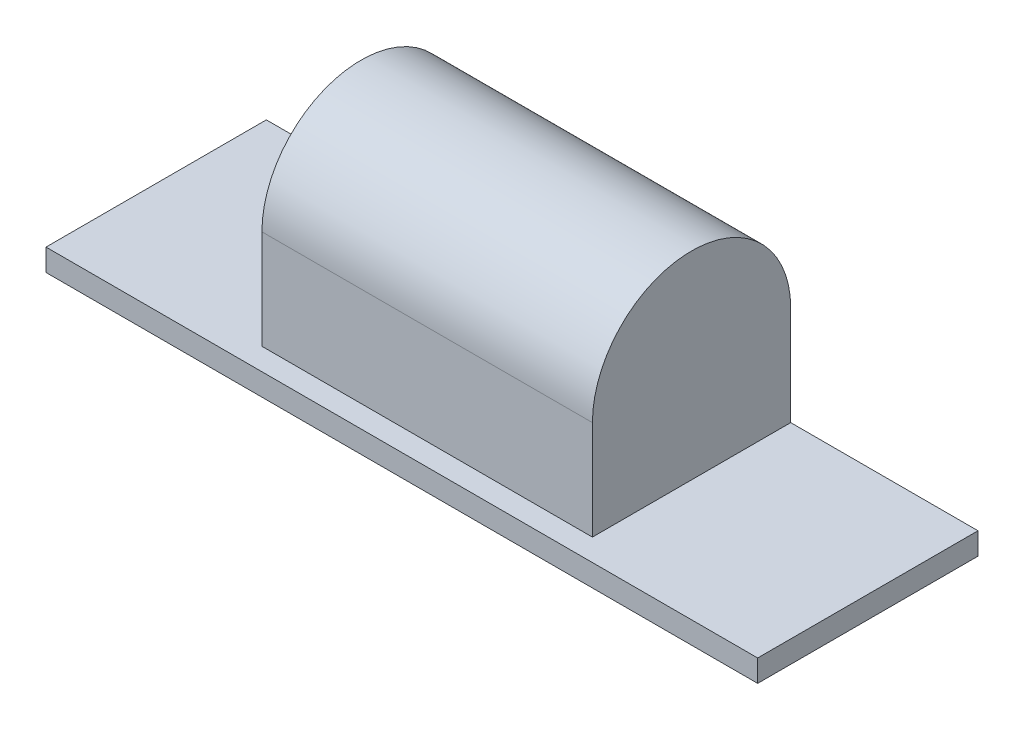
SolidWorks part; units mm, degrees
ref_plane "Front Plane" through (0, 0, 0) normal (0, 0, 1) x (1, 0, 0)
ref_plane "Top Plane" through (0, 0, 0) normal (0, 1, 0) x (1, 0, 0)
ref_plane "Right Plane" through (0, 0, 0) normal (1, 0, 0) x (0, 0, -1)
sketch "Sketch1" plane through (0, 0, 0) normal (0, 1, 0) x (1, 0, 0)
  line L1 (-32.0145, 14.529) -> (32.5855, 14.529)
  line L2 (-32.0145, 14.529) -> (-32.0145, -5.471)
  line L3 (-32.0145, -5.471) -> (32.5855, -5.471)
  line L4 (32.5855, 14.529) -> (32.5855, -5.471)
  line L5 (-14.4145, 14.529) -> (15.5855, 14.529)
  line L6 (-14.4145, 14.529) -> (-14.4145, -3.471)
  line L7 (-14.4145, -3.471) -> (15.5855, -3.471)
  line L8 (15.5855, 14.529) -> (15.5855, -3.471)
  dimension "D1" = 64.6
  dimension "D2" = 20
  dimension "D3" = 18
  dimension "D4" = 30
  dimension "D5" = 17
extrude "Boss-Extrude1" add sketch "Sketch1" along normal blind 2 contours L1 L8 L7 L6 L2 L3 L4 region at (-23.2145, 0, -13.8527)
extrude "Boss-Extrude2" add sketch "Sketch1<3>" along normal blind 20 contours L8 L1 L6 L7 region at (0.5855, 0, -5.529)
sketch "Sketch1<3>" plane through (0, 0, 0) normal (0, 1, 0) x (1, 0, 0) same geometry as "Sketch1"
sketch "Sketch2" plane through (-14.4145, 0, 0) normal (-1, 0, 0) x (0, 0, 1)
  line L0 (-14.529, 11) -> (-14.529, 20)
  line L1 (-14.529, 20) -> (3.471, 20)
  line L2 (3.471, 20) -> (3.471, 11)
  circle A0 centre (-5.529, 11) radius 9
  line M2 (3.471, 2) -> (3.471, 20)
  line M3 (3.471, 20) -> (-14.529, 20)
  line M4 (-14.529, 20) -> (-14.529, 2)
extrude "Cut-Extrude1" cut sketch "Sketch2" against normal through all contours A0 L1 M4 | A0 M2 M3 region at (-14.4145, 17.9897, -12.5186) region at (-14.4145, 17.9897, 1.4607)
